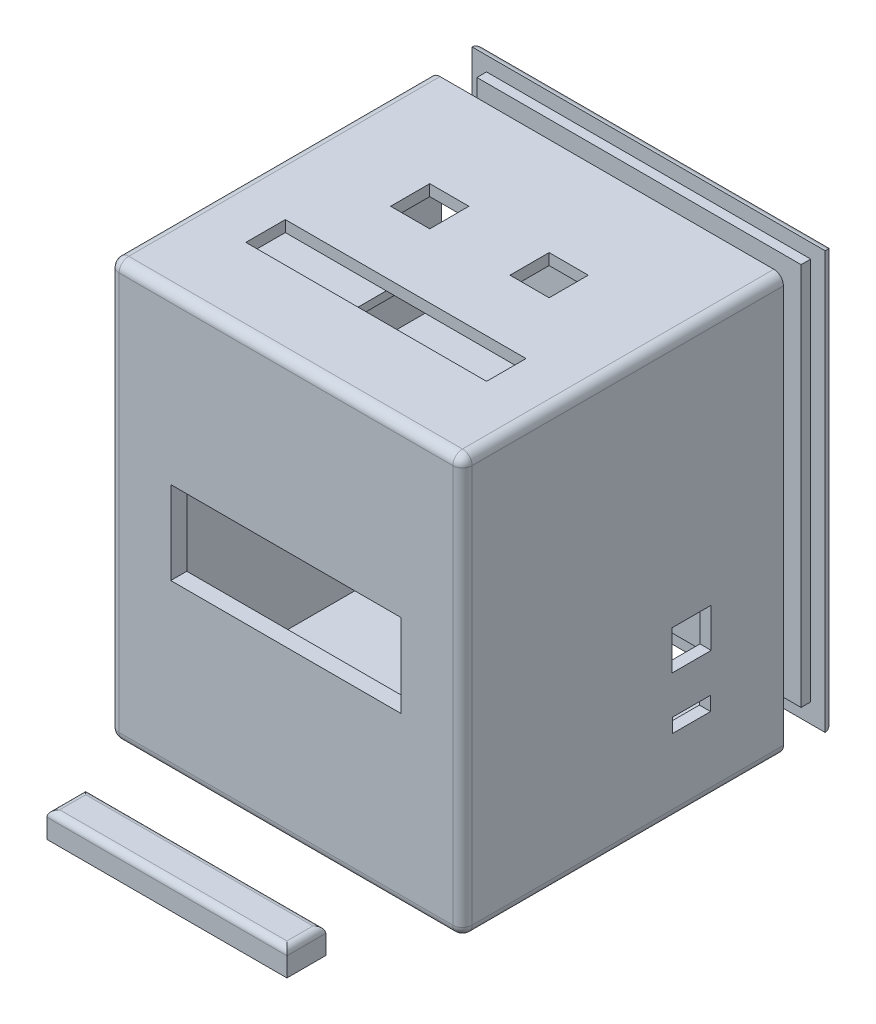
SolidWorks part; units mm, degrees
ref_plane "Front Plane" through (0, 0, 0) normal (0, 0, 1) x (1, 0, 0)
ref_plane "Top Plane" through (0, 0, 0) normal (0, 1, 0) x (1, 0, 0)
ref_plane "Right Plane" through (0, 0, 0) normal (1, 0, 0) x (0, 0, -1)
sketch "Sketch1" plane through (0, 0, 0) normal (0, 1, 0) x (1, 0, 0)
  line L1 (0, 0) -> (110, 0)
  line L2 (0, 0) -> (0, 100)
  line L3 (0, 100) -> (110, 100)
  line L4 (110, 0) -> (110, 100)
  dimension "D1" = 110
  dimension "D2" = 100
extrude "Boss-Extrude1" add sketch "Sketch1" along normal blind 130
sketch "Sketch2" plane through (0, 0, -100) normal (0, 0, -1) x (-1, 0, 0)
  line L0 (0, 130) -> (0, 0) construction
  line L1 (-106.5, 126.5) -> (-3.5, 126.5)
  line L2 (-106.5, 126.5) -> (-106.5, 5)
  line L3 (-106.5, 5) -> (-3.5, 5)
  line L4 (-3.5, 126.5) -> (-3.5, 5)
  line L5 (-110, 0) -> (0, 0) construction
  line L6 (-110, 130) -> (0, 130) construction
  line L7 (-110, 130) -> (-110, 0) construction
  dimension "D1" = 3.5
  dimension "D2" = 5
  dimension "D3" = 3.5
  dimension "D4" = 3.5
extrude "Cut-Extrude1" cut sketch "Sketch2" against normal offset from surface (95 mm away) 5 up to face at (55, 65, 0)
sketch "Sketch3" plane through (0, 0, 0) normal (0, 0, 1) x (1, 0, 0)
  line L0 (0, 0) -> (110, 0) construction
  line L1 (19.1, 77.95) -> (90.9, 77.95)
  line L2 (19.1, 77.95) -> (19.1, 52.05)
  line L3 (19.1, 52.05) -> (90.9, 52.05)
  line L4 (90.9, 77.95) -> (90.9, 52.05)
  line L5 (55, 0) -> (55, 52.05) construction
  line L6 (110, 65) -> (90.9, 65) construction
  line L7 (110, 130) -> (110, 0) construction
  dimension "D1" = 71.8
  dimension "D2" = 25.9
extrude "Cut-Extrude2" cut sketch "Sketch3" against normal up to surface (5 mm away) up to face at (55, 65.75, -5)
sketch "Sketch4" plane through (0, 130, 0) normal (0, 1, 0) x (1, 0, 0)
  line L0 (42.5, 63.4) -> (67.5, 63.4) construction
  line L1 (17.5, 37.3) -> (92.5, 37.3)
  line L2 (17.5, 37.3) -> (17.5, 25)
  line L3 (17.5, 25) -> (92.5, 25)
  line L4 (92.5, 37.3) -> (92.5, 25)
  line L5 (67.5, 69.5) -> (79.7, 69.5)
  line L6 (67.5, 69.5) -> (67.5, 57.3)
  line L7 (67.5, 57.3) -> (79.7, 57.3)
  line L8 (79.7, 69.5) -> (79.7, 57.3)
  line L9 (30.3, 69.5) -> (42.5, 69.5)
  line L10 (30.3, 69.5) -> (30.3, 57.3)
  line L11 (30.3, 57.3) -> (42.5, 57.3)
  line L12 (42.5, 69.5) -> (42.5, 57.3)
  line L13 (55, 25) -> (55, 0) construction
  line L14 (0, 0) -> (110, 0) construction
  line L15 (55, 63.4) -> (55, 37.3) construction
  dimension "D1" = 12.2
  dimension "D2" = 12.2
  dimension "D3" = 12.2
  dimension "D4" = 12.2
  dimension "D5" = 12.3
  dimension "D6" = 75
  dimension "D7" = 25
  dimension "D8" = 20
  dimension "D9" = 25
extrude "Cut-Extrude3" cut sketch "Sketch4" against normal up to surface (3.5 mm away) up to face at (55, 126.5, -52.5)
ref_plane "Plane1" through (0, 0, -110) normal (0, 0, -1) x (-1, 0, 0)
sketch "Sketch5" plane through (0, 0, -110) normal (0, 0, -1) x (-1, 0, 0)
  line L0 (-106.5, 126.5) -> (-3.5, 126.5) construction
  line L1 (-105.5, 125.5) -> (-4.5, 125.5)
  line L2 (-105.5, 125.5) -> (-105.5, 6)
  line L3 (-105.5, 6) -> (-4.5, 6)
  line L4 (-4.5, 125.5) -> (-4.5, 6)
  line L5 (-3.5, 126.5) -> (-3.5, 5) construction
  line L6 (-106.5, 5) -> (-3.5, 5) construction
  line L7 (-106.5, 126.5) -> (-106.5, 5) construction
  dimension "D1" = 1
  dimension "D2" = 1
  dimension "D3" = 1
  dimension "D4" = 1
extrude "Boss-Extrude2" add sketch "Sketch5" along normal blind 3 separate body
sketch "Sketch7" plane through (0, 0, -113) normal (0, 0, -1) x (-1, 0, 0)
  line L1 (-110, 130) -> (0, 130)
  line L2 (-110, 130) -> (-110, 0)
  line L3 (-110, 0) -> (0, 0)
  line L4 (0, 130) -> (0, 0)
extrude "Boss-Extrude3" add sketch "Sketch7" along normal blind 3
sketch "Sketch8" plane through (110, 0, 0) normal (1, 0, 0) x (0, 0, -1)
  line L0 (71.4, 39.9) -> (71.4, 27.9) construction
  line L1 (65.5, 27.9) -> (77.3, 27.9)
  line L2 (65.5, 27.9) -> (65.5, 23.5)
  line L3 (65.5, 23.5) -> (77.3, 23.5)
  line L4 (77.3, 27.9) -> (77.3, 23.5)
  line L5 (65.3, 52.1) -> (77.5, 52.1)
  line L6 (65.3, 52.1) -> (65.3, 39.9)
  line L7 (65.3, 39.9) -> (77.5, 39.9)
  line L8 (77.5, 52.1) -> (77.5, 39.9)
  line L10 (0, 0) -> (100, 0) construction
  line L11 (100, 130) -> (100, 0) construction
  dimension "D1" = 12.2
  dimension "D2" = 12.2
  dimension "D3" = 11.8
  dimension "D4" = 4.4
  dimension "D5" = 34.5
  dimension "D6" = 23.5
  dimension "D7" = 12
extrude "Cut-Extrude4" cut sketch "Sketch8" against normal up to surface (3.5 mm away) up to face at (106.5, 65.75, -52.5)
sketch "Sketch9" plane through (0, 0, -116) normal (0, 0, -1) x (-1, 0, 0)
  line L2 (-110, 130) -> (-110, 0) construction
  line L3 (-86, 35.7) -> (-76.2, 35.7)
  line L4 (-86, 35.7) -> (-86, 23.6)
  line L5 (-86, 23.6) -> (-76.2, 23.6)
  line L6 (-76.2, 35.7) -> (-76.2, 23.6)
  line L7 (-110, 0) -> (0, 0) construction
  dimension "D1" = 24
  dimension "D2" = 23.6
  dimension "D4" = 9.8
  dimension "D5" = 12.1
extrude "Cut-Extrude5" cut sketch "Sketch9" against normal up to surface (6 mm away) up to face at (55, 65.75, -110)
sketch "Sketch10" plane through (0, 0, 0) normal (0, 1, 0) x (1, 0, 0)
  line L1 (17.6, -25) -> (92.4, -25)
  line L2 (17.6, -25) -> (17.6, -37.1)
  line L3 (17.6, -37.1) -> (92.4, -37.1)
  line L4 (92.4, -25) -> (92.4, -37.1)
  line L6 (55, -25) -> (55, 0) construction
  line L7 (0, 0) -> (110, 0) construction
  dimension "D1" = 74.8
  dimension "D2" = 12.1
  dimension "D3" = 25
extrude "Boss-Extrude4" add sketch "Sketch10" along normal blind 8 separate body
sketch "Sketch11" plane through (0, 0, 0) normal (0, -1, 0) x (1, 0, 0)
  line L0 (55, 37.1) -> (55, 25) construction
  line L1 (17.6, 37.1) -> (92.4, 37.1) construction
  line L2 (92.4, 25) -> (17.6, 25) construction
  circle A0 centre (55, 31.05) radius 3.35
  point P9 (55, 31.05)
  dimension "D1" = 6.7
extrude "Cut-Extrude6" cut sketch "Sketch11" against normal blind 3.5
fillet "Fillet1" radius 3 9 edges at (110, 0, -50) (0, 0, -50) (55, 5, -5) (0, 65, 0) (110, 65, 0) (110, 130, -50) (55, 130, 0) (0, 130, -50) (55, 0, 0)
fillet "Fillet2" radius 3 4 edges at (55, 0, -116) (110, 65, -116) (0, 65, -116) (55, 130, -116)
fillet "Fillet3" radius 2 4 edges at (17.6, 8, 31.05) (92.4, 8, 31.05) (55, 8, 25) (55, 8, 37.1)
sketch "Sketch13" plane through (0, 126.5, 0) normal (0, -1, 0) x (1, 0, 0)
  line L0 (61.05, -31.15) -> (48.95, -31.15) construction
  line L1 (13.95, -21.15) -> (48.95, -21.15)
  line L2 (13.95, -21.15) -> (13.95, -41.15)
  line L3 (13.95, -41.15) -> (48.95, -41.15)
  line L4 (48.95, -21.15) -> (48.95, -41.15)
  line L5 (61.05, -21.15) -> (96.05, -21.15)
  line L6 (61.05, -21.15) -> (61.05, -41.15)
  line L7 (61.05, -41.15) -> (96.05, -41.15)
  line L8 (96.05, -21.15) -> (96.05, -41.15)
  line L11 (55, -31.15) -> (55, 0) construction
  line L12 (0, 0) -> (110, 0) construction
  point P14 (13.95, -31.15)
  dimension "D1" = 12.1
  dimension "D2" = 20
  dimension "D3" = 20
  dimension "D4" = 35
  dimension "D5" = 35
  dimension "D6" = 31.15
extrude "Boss-Extrude5" add sketch "Sketch13" along normal blind 2.5
